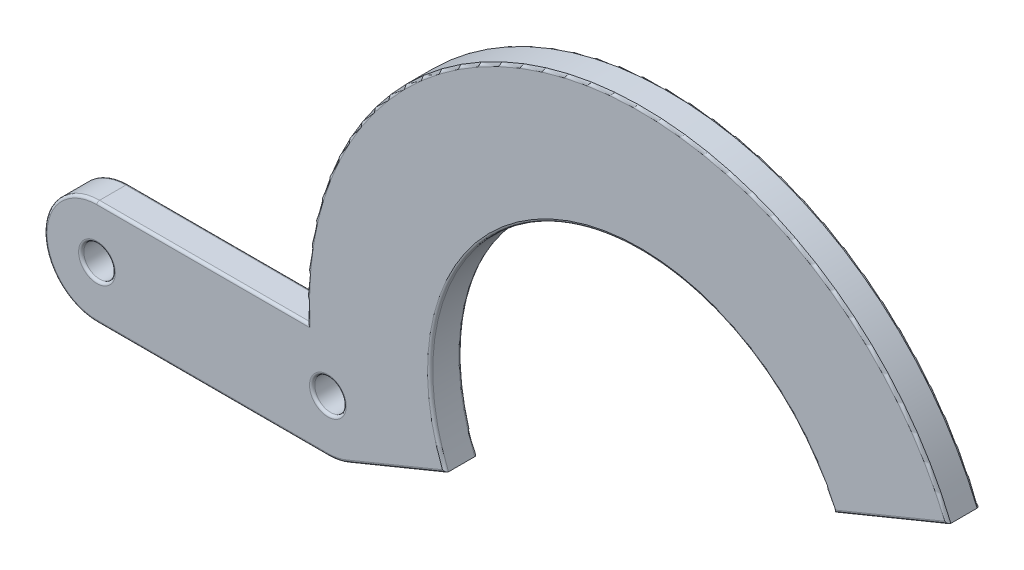
SolidWorks part; units mm, degrees
ref_plane "Front Plane" through (0, 0, 0) normal (0, 0, 1) x (1, 0, 0)
ref_plane "Top Plane" through (0, 0, 0) normal (0, 1, 0) x (1, 0, 0)
ref_plane "Right Plane" through (0, 0, 0) normal (1, 0, 0) x (0, 0, -1)
sketch "Sketch3" plane through (0, 0, 0) normal (0, 0, 1) x (1, 0, 0)
  line L0 (0, 0) -> (22, 0) construction
  line L1 (0, 5) -> (22, 5)
  line L2 (0, -5) -> (22, -5)
  line L3 (20.05, 5) -> (23.9914, -4.5863) construction
  line L4 (20.05, 5) -> (66.2939, 24.0132) construction
  line L5 (23.9914, -4.5863) -> (70.2353, 14.4269) construction
  line L6 (66.2939, 24.0132) -> (70.2353, 14.4269) construction
  line L7 (70.2353, 14.4269) -> (84.0705, 20.1152) construction
  line L8 (81.0935, 18.8912) -> (70.2353, 14.4269)
  line L9 (68.364, 18.5193) -> (70.2353, 14.4269)
  line L10 (70.2353, 14.4269) -> (33.2402, -0.7837) construction
  line L13 (23.9914, -4.5863) -> (33.2402, -0.7837)
  arc A0 (0, 5) -> (0, -5) centre (0, 0) ccw
  arc A1 (22, -5) -> (22, 5) centre (22, 0) ccw
  circle A2 centre (0, 0) radius 1.5
  circle A3 centre (22, 0) radius 1.5
  arc A4 (33.2402, -0.7837) -> (70.2353, 14.4269) centre (51.7378, 6.8216) cw
  arc A6 (81.0935, 18.8912) -> (20.05, 5) centre (51.7378, 6.8216) ccw
  point P3 (11, 0)
  dimension "D12" = 3
  dimension "D1" = 22
  dimension "D2" = 10
  dimension "D3" = 50
  dimension "D4" = 1.95
  dimension "D5" = 157.65
  dimension "D8" = 40
  dimension "D9" = 4.5
extrude "Boss-Extrude1" add sketch "Sketch3" along normal blind 3 contours A1 L1 A0 L2 A3 A2 | A1 L9 L1 region at (11, 0, 0) region at (44.8609, 37.0411, 0)
fillet "Fillet1" radius 0.25 20 edges at (23.017, -4.8955, 0) (28.6158, -2.685, 0) (44.1325, 25.3192, 0) (75.6644, 16.659, 0) (44.695, 37.7704, 0) (10.025, 5, 0) (-5, 0, 0) (11, -5, 0) (1.5, 0, 0) (23.5, 0, 0) (-5, 0, 3) (10.025, 5, 3) (44.695, 37.7704, 3) (75.6644, 16.659, 3) (44.1325, 25.3192, 3) (28.6158, -2.685, 3) (23.017, -4.8955, 3) (11, -5, 3) (1.5, 0, 3) (23.5, 0, 3)
